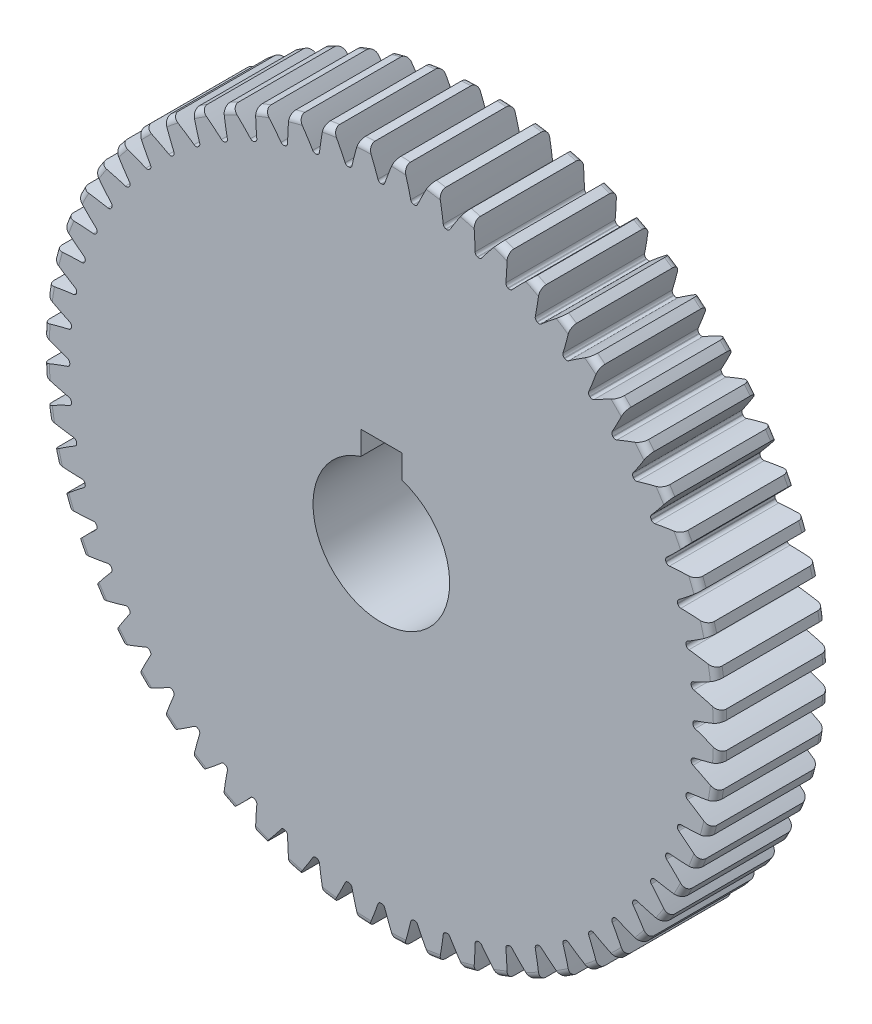
SolidWorks part; units mm, degrees
ref_plane "Front Plane" through (0, 0, 0) normal (0, 0, 1) x (1, 0, 0)
ref_plane "Top Plane" through (0, 0, 0) normal (0, 1, 0) x (1, 0, 0)
ref_plane "Right Plane" through (0, 0, 0) normal (1, 0, 0) x (0, 0, -1)
sketch "Sketch1" plane through (0, 0, 0) normal (0, 0, 1) x (1, 0, 0)
  line L0 (-762, 0) -> (762, 0) construction
  circle A0 centre (0, 0) radius 39.37 construction
  circle A1 centre (0, 0) radius 38.1 construction
  circle A2 centre (0, 0) radius 36.195 construction
  circle A3 centre (0, 0) radius 26.924 construction
  circle A4 centre (0, 0) radius 6.35 construction
  dimension "D2" = 1.27
  dimension "D3" = 3.175
  dimension "D1" = 3.175
sketch "Sketch2" plane through (0, 0, 0) normal (1, 0, 0) x (0, 0, -1)
  line L0 (0, 0) -> (-12.7, 0) construction
  line L1 (-12.7, 0) -> (-25.4, 0) construction
  dimension "Overall Width" = 25.4
  dimension "Face Width" = 12.7
sketch "Sketch4" plane through (0, 0, 0) normal (1, 0, 0) x (0, 0, -1)
  line L0 (-25.4, 6.35) -> (-25.4, 26.924)
  line L1 (-25.4, 26.924) -> (-12.7, 26.924)
  line L2 (-12.7, 26.924) -> (-12.7, 39.37)
  line L3 (-12.7, 39.37) -> (0, 39.37)
  line L4 (0, 39.37) -> (0, 6.35)
  line L5 (-12.7, 26.924) -> (-12.7, 0) construction
  line L6 (0, 39.37) -> (0, -39.37) construction
  line L7 (-12.7, 26.924) -> (0, 26.924) construction
  line L12 (-25.4, 6.35) -> (0, 6.35)
revolve "Revolve1" add sketch "Sketch4" angle 360 about L1
fillet "Fillet2" radius 0.7874 4 edges at (0, 26.924, 25.4) (0, 26.924, 12.7) (0, 39.37, 12.7) (0, 39.37, 0)
sketch "Sketch7" plane through (0, 0, 12.7) normal (0, 0, 1) x (1, 0, 0)
  line L0 (0, 0) -> (0, 39.37) construction
  line L1 (0.9973, 38.0869) -> (1.4916, 39.3417) construction
  line L3 (2.0605, 39.316) -> (1.994, 38.0478) construction
  line L4 (1.994, 38.0478) -> (1.8943, 36.1454) construction
  line L5 (0, 0) -> (1.8943, 36.1454) construction
  line L6 (0.9973, 38.0869) -> (0, 0) construction
  line L7 (0.9973, 38.0869) -> (1.0306, 39.3565) construction
  line L8 (0.9973, 38.0869) -> (0, 0) construction
  circle A0 centre (0, 0) radius 39.37 construction
  arc A1 (-0.0355, 36.195) -> (0.0355, 36.195) centre (0, 0) cw
  circle A2 centre (0, 0) radius 36.195 construction
  arc A3 (-0.9973, 38.0869) -> (0.9973, 38.0869) centre (0, 0) cw construction
  circle A4 centre (0, 0) radius 38.1 construction
  arc A5 (2.6033, 39.2838) -> (1.5172, 39.3408) centre (0, 0) ccw construction
  arc A6 (0.9973, 38.0869) -> (2.9893, 37.9826) centre (0, 0) cw construction
  arc A7 (-1.5172, 39.3408) -> (1.5172, 39.3408) centre (0, 0) cw
  arc A8 (0.3964, 36.4527) -> (1.5172, 39.3408) centre (36.4463, 24.1232) cw
  arc A9 (-0.3964, 36.4527) -> (-1.5172, 39.3408) centre (-36.4463, 24.1232) ccw
  arc A10 (-0.0355, 36.195) -> (-0.3964, 36.4527) centre (-0.0358, 36.576) cw
  arc A11 (0.0355, 36.195) -> (0.3964, 36.4527) centre (0.0358, 36.576) ccw
  point P26 (-0.3088, 36.1937)
  point P29 (0.3088, 36.1937)
  dimension "D4" = 0.381
  dimension "D5" = 38.1
  dimension "D3" = 20
  dimension "D1" = 3.9898
  dimension "D2" = 1.9949
extrude "Cut-Extrude2" cut sketch "Sketch7" against normal through all
pattern_circular "CirPattern1" count 60 over 360 about axis through (0, 0, 25.4) along (0, 0, -1) of "Cut-Extrude2"
sketch "Sketch8" plane through (0, 0, 0) normal (0, 0, -1) x (-1, 0, 0)
  circle A0 centre (0, 0) radius 7.9375
  dimension "D1" = 15.875
extrude "Cut-Extrude3" cut sketch "Sketch8" against normal up to next
sketch "Sketch9" plane through (0, 0, 25.4) normal (0, 0, 1) x (1, 0, 0)
  circle A0 centre (0, 0) radius 29.21
  dimension "D1" = 58.42
extrude "Cut-Extrude4" cut sketch "Sketch9" against normal up to surface (12.7 mm away) up to face at (0, 0, 12.7)
sketch "Sketch10" plane through (0, 0, 12.7) normal (0, 0, 1) x (1, 0, 0)
  line L0 (0, 0) -> (0, 29.2025) construction
  line L1 (-2.3813, 10.3187) -> (2.3813, 10.3187)
  line L2 (-2.3813, 10.3187) -> (-2.3813, 5.5562)
  line L3 (-2.3813, 5.5562) -> (2.3813, 5.5563)
  line L4 (2.3813, 10.3187) -> (2.3813, 5.5563)
  line L5 (0, 10.3187) -> (0, 5.5562) construction
  line L6 (0, 7.9375) -> (-19.3624, 7.9375) construction
  circle A0 centre (0, 0) radius 7.9375 construction
  circle A1 centre (0, 0) radius 7.9375
  dimension "D1" = 4.7625
  dimension "D2" = 4.7625
  dimension "D3" = 2.3812
extrude "Cut-Extrude5" cut sketch "Sketch10" against normal up to next contours A1 L4 L1 L2 region at (0, 9.0654, 12.7)
equation "\"D1@Sketch1\"=2.5*(\"Pitch Dia.@Sketch1\"/\"Number of Teeth@Sketch1\")"
equation "\"D1@CirPattern1\"=\"Number of Teeth@Sketch1\""
equation "\"D1@Fillet2\"=\"OD@Sketch1\"*.01"
equation "\"D1@Sketch7\"=3.14159*(\"Pitch Dia.@Sketch1\"/\"Number of Teeth@Sketch1\")"
equation "\"D2@Sketch7\"=\"D1@Sketch7\"/2"
equation "\"D4@Sketch7\"=\"D1@Sketch7\"*.0955"
equation "\"D5@Sketch7\"=\"Pitch Dia.@Sketch1\"/2"
